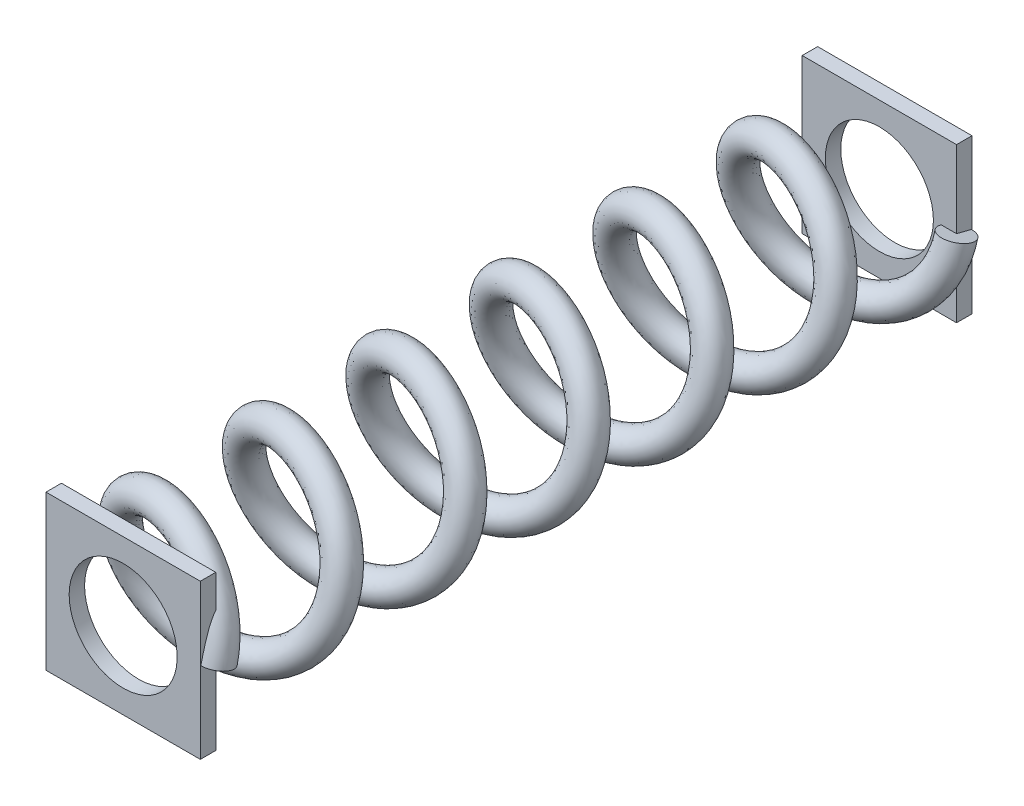
SolidWorks part; units mm, degrees
ref_plane "前视基准面" through (0, 0, 0) normal (0, 0, 1) x (1, 0, 0)
ref_plane "上视基准面" through (0, 0, 0) normal (0, 1, 0) x (1, 0, 0)
ref_plane "右视基准面" through (0, 0, 0) normal (1, 0, 0) x (0, 0, -1)
sketch "草图1" plane through (0, 0, 0) normal (0, 0, 1) x (1, 0, 0)
  circle A0 centre (0, 0) radius 5
curve "螺旋线/涡状线1" pitch 8 height 48 radius 5 left hand yes centre (0, 0, 0) axis (0, 0, 1) start towards (1, 0, 0)
sketch "草图2" plane through (0, 0, 0) normal (0, 1, 0) x (1, 0, 0)
  circle A0 centre (4.9944, 0) radius 1
sweep "扫描1" add path "螺旋线/涡状线1" circular profile diameter 2 parameters "D3"=2
sketch "草图19" plane through (0, 0, 0) normal (0, 0, 1) x (1, 0, 0)
  line L0 (0, 5) -> (-5, 5)
  line L1 (-5, 5) -> (-5, -5)
  line L2 (-5, -5) -> (5, -5)
  line L3 (5, -5) -> (5, 5)
  line L4 (5, 5) -> (0, 5)
  circle A0 centre (0, 0) radius 5
extrude "凸台-拉伸1" add sketch "草图19" against normal blind 1 contours A0 | A0 L3 L4 | A0 L2 L3 | A0 L1 L2 | A0 L0 L1 region at (-3.8832, 3.8832, 0) region at (3.8832, 3.8832, 0) region at (0, 0, 0) region at (3.8832, -3.8832, 0) region at (-3.8832, -3.8832, 0)
sketch "草图20" plane through (0, 0, -1) normal (0, 0, -1) x (-1, 0, 0)
  circle A0 centre (0, 0) radius 3.5
sketch "草图23" plane through (0, 0, -1) normal (0, 0, -1) x (-1, 0, 0)
  circle A0 centre (0, 0) radius 3.5
extrude "凸台-拉伸2" add sketch "草图23" against normal blind 49
sketch "草图24" plane through (0, 0, 48) normal (0, 0, 1) x (1, 0, 0)
  line L0 (0, 5) -> (5, 5)
  line L1 (5, 5) -> (5, -5)
  line L2 (5, -5) -> (-5, -5)
  line L3 (-5, -5) -> (-5, 5)
  line L4 (-5, 5) -> (0, 5)
  circle A0 centre (0, 0) radius 5
  circle M2 centre (0, 0) radius 3.5
extrude "凸台-拉伸3" add sketch "草图24" along normal blind 1 contours A0 L4 L3 | A0 L1 L0 | A0 M2 | A0 L3 L2 | A0 L2 L1 | M2 region at (-3.8832, 3.8832, 48) region at (3.8832, 3.8832, 48) region at (3.4355, 3.4355, 48) region at (3.8832, -3.8832, 48) region at (-3.8832, -3.8832, 48) region at (0, 0, 48)
sketch "草图26" plane through (0, 0, -1) normal (0, 0, -1) x (-1, 0, 0)
  circle A0 centre (0, 0) radius 3.5
extrude "切除-拉伸1" cut sketch "草图26" against normal blind 50
